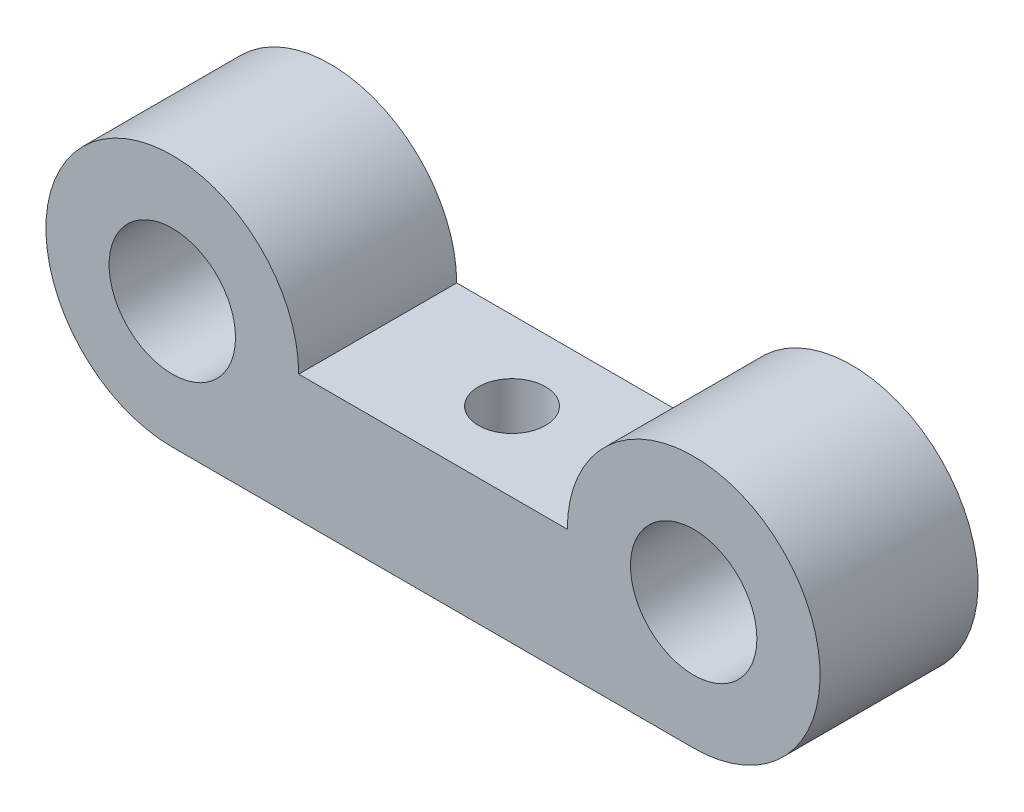
SolidWorks part; units mm, degrees
material "ABS"
ref_plane "Plano frontal" through (0, 0, 0) normal (0, 0, 1) x (1, 0, 0)
ref_plane "Plano superior" through (0, 0, 0) normal (0, 1, 0) x (1, 0, 0)
ref_plane "Plano direito" through (0, 0, 0) normal (1, 0, 0) x (0, 0, -1)
sketch "Esboço1" plane through (0, 0, 0) normal (0, 0, 1) x (1, 0, 0)
  line L0 (-16.5, 0) -> (16.5, 0) construction
  line L1 (-16.5, 0) -> (16.5, 0) construction
  line L3 (-16.5, -8) -> (16.5, -8)
  line L4 (0, 0) -> (0, 11.918) construction
  line L10 (-8.5, 0) -> (8.5, 0)
  circle A0 centre (-16.5, 0) radius 4
  circle A1 centre (16.5, 0) radius 4
  arc A2 (-8.5, 0) -> (-16.5, -8) centre (-16.5, 0) ccw
  arc A3 (16.5, -8) -> (8.5, 0) centre (16.5, 0) ccw
  point P4 (0, 0)
  point P6 (0, 0)
  dimension "D2" = 8
  dimension "D3" = 8
  dimension "D1" = 33
extrude "Ressalto-extrusão1" add sketch "Esboço1" along normal blind 10
sketch "Esboço2" plane through (0, 0, 0) normal (0, 1, 0) x (1, 0, 0)
  line L0 (8.5, -5) -> (-8.5, -5) construction
  line L1 (8.5, -10) -> (8.5, 0) construction
  line L2 (-8.5, -10) -> (-8.5, 0) construction
  circle A0 centre (0, -5) radius 2.125
extrude "Corte-extrusão1" cut sketch "Esboço2" against normal blind 10 contours A0
